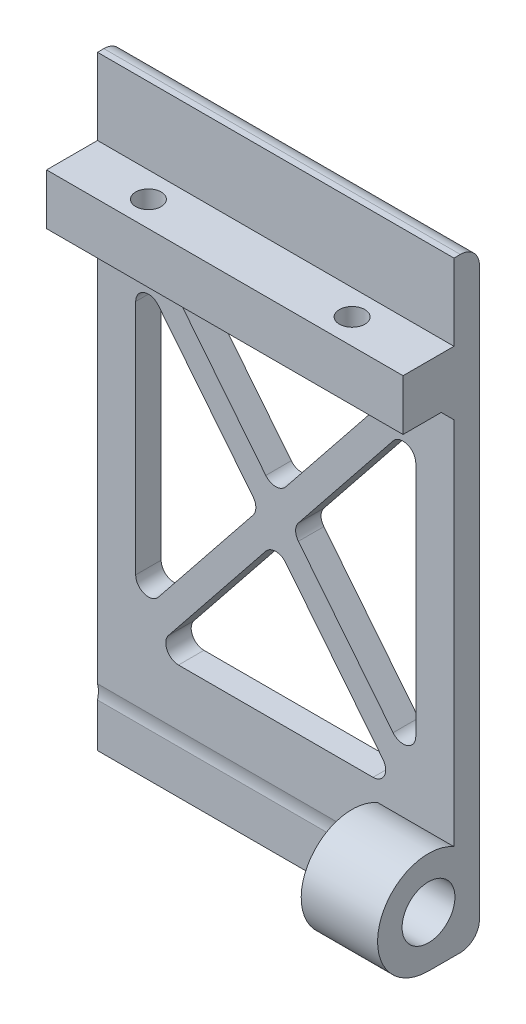
SolidWorks part; units mm, degrees
material "ABS"
ref_plane "前视基准面" through (0, 0, 0) normal (0, 0, 1) x (1, 0, 0)
ref_plane "上视基准面" through (0, 0, 0) normal (0, 1, 0) x (1, 0, 0)
ref_plane "右视基准面" through (0, 0, 0) normal (1, 0, 0) x (0, 0, -1)
other "Configuration Table"
sketch "草图1" plane through (0, 0, 0) normal (1, 0, 0) x (0, 0, -1)
  line L0 (-16.4301, -8) -> (8, -8)
  line L1 (8, -8) -> (8, 87)
  line L2 (8, 87) -> (4, 87)
  line L3 (4, 87) -> (4, 75)
  line L4 (4, 75) -> (-4, 75)
  line L5 (-4, 75) -> (-4, 67)
  line L6 (-4, 67) -> (4, 67)
  line L7 (4, 67) -> (4, 6.9282)
  circle A0 centre (0, 0) radius 4.15
  circle A1 centre (0, 0) radius 8
  dimension "D1" = 8.3
  dimension "D3" = 8
  dimension "D9" = 16
  dimension "D2" = 8
  dimension "D4" = 4
  dimension "D5" = 95
  dimension "D6" = 12
  dimension "D7" = 8
  dimension "D8" = 8
extrude "凸台-拉伸1" add sketch "草图1" along normal blind 56 contours A1 L1 L2 L3 L4 L5 L6 L7 | A1 A0 | A1 L0 L1 region at (0, -6.2131, -6.2131) region at (0, 2.012, 7.5088) region at (0, 50.029, -5.0393)
fillet "圆角1" radius 3 2 edges at (28, 87, -8) (28, -8, -8)
sketch "草图2" plane through (0, 0, 0) normal (-1, 0, 0) x (0, 0, 1)
  line L0 (-4, 6.9282) -> (-4, -8)
  line L1 (0, -8) -> (-5, -8) construction
  line L10 (-4, 87) -> (-5, 87)
  line L11 (-8, 84) -> (-8, -5)
  line L12 (-5, -8) -> (0, -8)
  line L13 (-4, 6.9282) -> (-4, 67)
  line L14 (-4, 67) -> (4, 67)
  line L15 (4, 67) -> (4, 75)
  line L16 (4, 75) -> (-4, 75)
  line L17 (-4, 75) -> (-4, 87)
  line L18 (-4, 87) -> (-5, 87)
  line L19 (-8, 84) -> (-8, -5)
  line L20 (-5, -8) -> (0, -8)
  line L21 (-4, 6.9282) -> (-4, 67)
  line L22 (-4, 67) -> (4, 67)
  line L23 (4, 67) -> (4, 75)
  line L24 (4, 75) -> (-4, 75)
  line L25 (-4, 75) -> (-4, 87)
  arc A4 (-5, 87) -> (-8, 84) centre (-5, 84) ccw
  arc A5 (-8, -5) -> (-5, -8) centre (-5, -5) ccw
  arc A6 (0, -8) -> (-4, 6.9282) centre (0, 0) ccw
  arc A7 (-5, 87) -> (-8, 84) centre (-5, 84) ccw
  arc A8 (-8, -5) -> (-5, -8) centre (-5, -5) ccw
  arc A9 (0, -8) -> (-4, 6.9282) centre (0, 0) ccw
  line M16 (-5, -8) -> (0, -8)
  arc M17 (0, -8) -> (-4, 6.9282) centre (0, 0) ccw
  circle M23 centre (0, 0) radius 4.15
  dimension "D1" = 0
extrude "切除-拉伸1" cut sketch "草图2" against normal blind 44 contours L0 M17 M23 M16 region at (0, 2.0188, 7.5342)
sketch "草图3" plane through (0, 0, -4) normal (0, 0, 1) x (1, 0, 0)
  line L0 (44, 8) -> (0, 8) construction
  line L1 (14.1436, 57.5) -> (22.5889, 42.8724)
  line L2 (0, 67) -> (0, 1.1057) construction
  line L3 (28, 67) -> (28, 8) construction
  line L4 (56, 67) -> (0, 67) construction
  line L5 (15.8756, 58.5) -> (22.8038, 46.5) construction
  line L6 (38.3923, 37.5) -> (33.1962, 46.5)
  line L7 (33.1962, 46.5) -> (22.8038, 46.5)
  line L8 (22.8038, 46.5) -> (17.6077, 37.5)
  line L9 (17.6077, 37.5) -> (22.8038, 28.5)
  line L10 (22.8038, 28.5) -> (33.1962, 28.5)
  line L11 (33.1962, 28.5) -> (38.3923, 37.5)
  line L12 (52.2487, 37.5) -> (40.1244, 58.5)
  line L13 (40.1244, 58.5) -> (15.8756, 58.5)
  line L14 (15.8756, 58.5) -> (3.7513, 37.5)
  line L15 (3.7513, 37.5) -> (15.8756, 16.5)
  line L16 (15.8756, 16.5) -> (40.1244, 16.5)
  line L17 (40.1244, 16.5) -> (52.2487, 37.5)
  line L18 (40.1244, 58.5) -> (33.1962, 46.5) construction
  line L19 (38.3923, 37.5) -> (52.2487, 37.5) construction
  line L20 (33.1962, 28.5) -> (40.1244, 16.5) construction
  line L21 (22.8038, 28.5) -> (15.8756, 16.5) construction
  line L22 (17.6077, 37.5) -> (3.7513, 37.5) construction
  line L23 (38.3923, 59.5) -> (30.1226, 45.1764)
  line L24 (34.9282, 37.5) -> (31.4641, 43.5)
  line L25 (31.4641, 43.5) -> (24.5359, 43.5)
  line L26 (24.5359, 43.5) -> (21.0718, 37.5)
  line L27 (21.0718, 37.5) -> (24.5359, 31.5)
  line L28 (24.5359, 31.5) -> (31.4641, 31.5)
  line L29 (31.4641, 31.5) -> (34.9282, 37.5)
  line L30 (21.0718, 39.5) -> (3.7513, 39.5)
  line L31 (22.2269, 31.5006) -> (14.1436, 17.5)
  line L32 (30.1194, 29.8291) -> (38.3923, 15.5)
  line L33 (35.2754, 35.5) -> (52.2487, 35.5)
  line L34 (17.6077, 59.5) -> (25.8849, 45.1634)
  line L35 (41.8564, 57.5) -> (33.7653, 43.4858)
  line L36 (20.7056, 35.5) -> (3.7513, 35.5)
  line L37 (26.2297, 30.4338) -> (17.6077, 15.5)
  line L38 (33.7715, 31.5035) -> (41.8564, 17.5)
  line L39 (35.7942, 39.5) -> (52.2487, 39.5)
  line L40 (14.1436, 57.5) -> (21.0718, 45.5) construction
  line L41 (17.6077, 59.5) -> (24.5359, 47.5) construction
  line L42 (38.3923, 59.5) -> (31.4641, 47.5) construction
  line L43 (41.8564, 57.5) -> (34.9282, 45.5) construction
  line L44 (38.3923, 39.5) -> (52.2487, 39.5) construction
  line L45 (38.3923, 35.5) -> (52.2487, 35.5) construction
  line L46 (34.9282, 29.5) -> (41.8564, 17.5) construction
  line L47 (31.4641, 27.5) -> (38.3923, 15.5) construction
  line L48 (24.5359, 27.5) -> (17.6077, 15.5) construction
  line L49 (21.0718, 29.5) -> (14.1436, 17.5) construction
  line L50 (17.6077, 35.5) -> (3.7513, 35.5) construction
  line L51 (17.6077, 39.5) -> (3.7513, 39.5) construction
  circle A0 centre (28, 37.5) radius 9 construction
  circle A1 centre (28, 37.5) radius 21 construction
  circle A2 centre (28, 37.5) radius 6 construction
  dimension "D1" = 18
  dimension "D3" = 12
  dimension "D4" = 2
  dimension "D5" = 2
extrude "切除-拉伸2" [suppressed] cut sketch "草图3" against normal blind 40 contours L13 L34 L7 L23 | L6 L39 L12 L35 | L11 L38 L17 L33 | L10 L37 L16 L32 | L9 L36 L15 L31 | L30 L8 L1 L14 | L28 L29 L24 L25 L26 L27
fillet "圆角2" [suppressed] radius 1
sketch "草图4" plane through (0, 0, -4) normal (0, 0, 1) x (1, 0, 0)
  line L0 (44, 8) -> (0, 8) construction
  line L1 (0, 67) -> (0, 1.1057) construction
  line L2 (28, 67) -> (28, 8) construction
  line L3 (56, 67) -> (0, 67) construction
  line L4 (51.5617, 11.2494) -> (7.5617, 66.2494)
  line L5 (50, 10) -> (6, 10)
  line L6 (50, 10) -> (50, 65)
  line L7 (50, 65) -> (6, 65)
  line L8 (6, 10) -> (6, 65)
  line L9 (50, 10) -> (6, 65) construction
  line L10 (50, 65) -> (6, 10) construction
  line L11 (48.4383, 66.2494) -> (4.4383, 11.2494)
  line L12 (48.4383, 8.7506) -> (4.4383, 63.7506)
  line L13 (51.5617, 63.7506) -> (7.5617, 8.7506)
  point P9 (28, 37.5)
  dimension "D1" = 2
  dimension "D2" = 6
  dimension "D3" = 2
  dimension "D4" = 2
extrude "切除-拉伸3" cut sketch "草图4" against normal blind 40 contours L11 L7 L4 | L11 L12 L8 | L12 L13 L5 | L6 L13 L4 region at (43.5204, 37.5, -4) region at (28, 56.9005, -4) region at (28, 18.0995, -4) region at (12.4796, 37.5, -4)
fillet "圆角3" radius 2 12 edges at (6, 13.2016, -6) (6, 61.7984, -6) (25.4388, 37.5, -6) (50, 61.7984, -6) (50, 13.2016, -6) (28, 40.7016, -6) (8.5612, 65, -6) (47.4388, 65, -6) (8.5612, 10, -6) (28, 34.2984, -6) (47.4388, 10, -6) (30.5612, 37.5, -6)
sketch "草图5" plane through (0, 67, 0) normal (0, -1, 0) x (1, 0, 0)
  arc A4 (4, -2) -> (4, 2) centre (4, 0) ccw construction
  arc A5 (4, 2) -> (4, -2) centre (4, 0) ccw construction
  arc A8 (52, -2) -> (52, 2) centre (52, 0) ccw construction
  arc A9 (52, 2) -> (52, -2) centre (52, 0) ccw construction
  arc A12 (44, -2) -> (44, 2) centre (44, 0) ccw
  arc A13 (44, 2) -> (44, -2) centre (44, 0) ccw
  arc A16 (12, -2) -> (12, 2) centre (12, 0) ccw
  arc A17 (12, 2) -> (12, -2) centre (12, 0) ccw
  arc A20 (20, -2) -> (20, 2) centre (20, 0) ccw construction
  arc A21 (20, 2) -> (20, -2) centre (20, 0) ccw construction
  arc A24 (28, -2) -> (28, 2) centre (28, 0) ccw construction
  arc A25 (28, 2) -> (28, -2) centre (28, 0) ccw construction
  arc A28 (36, -2) -> (36, 2) centre (36, 0) ccw construction
  arc A29 (36, 2) -> (36, -2) centre (36, 0) ccw construction
extrude "切除-拉伸4" cut sketch "草图5" against normal blind 40
sketch "草图6" plane through (0, 67, 0) normal (0, -1, 0) x (1, 0, 0)
  line L1 (16.1858, 0) -> (14.0929, 3.625)
  line L2 (14.0929, 3.625) -> (9.9071, 3.625)
  line L3 (9.9071, 3.625) -> (7.8142, 0)
  line L4 (7.8142, 0) -> (9.9071, -3.625)
  line L5 (9.9071, -3.625) -> (14.0929, -3.625)
  line L6 (14.0929, -3.625) -> (16.1858, 0)
  line L7 (39.8142, 0) -> (41.9071, -3.625)
  line L8 (41.9071, -3.625) -> (46.0929, -3.625)
  line L9 (46.0929, -3.625) -> (48.1858, 0)
  line L10 (48.1858, 0) -> (46.0929, 3.625)
  line L11 (46.0929, 3.625) -> (41.9071, 3.625)
  line L12 (41.9071, 3.625) -> (39.8142, 0)
  circle A0 centre (12, 0) radius 3.625 construction
  circle A1 centre (44, 0) radius 3.625 construction
  dimension "D1" = 7.25
extrude "切除-拉伸5" cut sketch "草图6" against normal blind 4
fillet "圆角4" radius 0.5 12 edges at (41.9071, 69, -3.625) (46.0929, 69, -3.625) (48.1858, 69, 0) (46.0929, 69, 3.625) (41.9071, 69, 3.625) (39.8142, 69, 0) (14.0929, 69, 3.625) (9.9071, 69, 3.625) (7.8142, 69, 0) (9.9071, 69, -3.625) (16.1858, 69, 0) (14.0929, 69, -3.625)
chamfer "倒角1" distance 2 angle 45 1 edges at (28, 67, -4)
